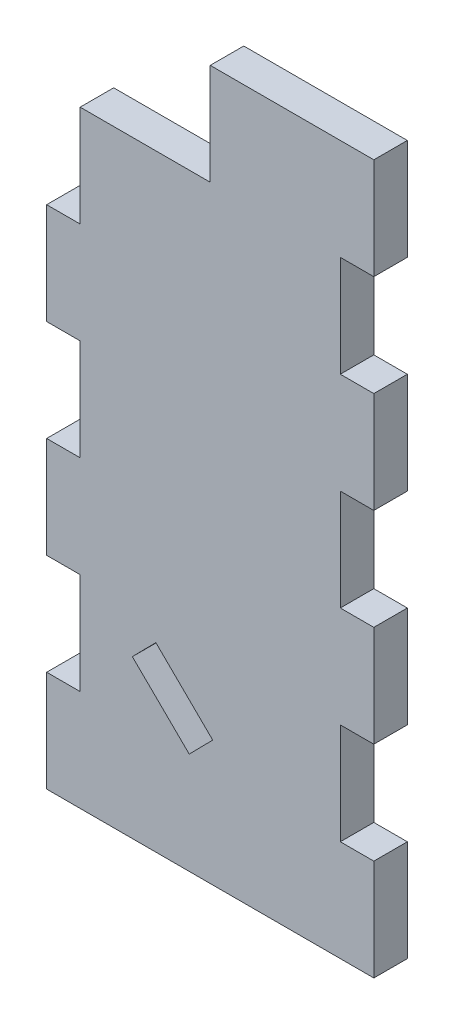
SolidWorks part; units mm, degrees
ref_plane "Front Plane" through (0, 0, 0) normal (0, 0, 1) x (1, 0, 0)
ref_plane "Top Plane" through (0, 0, 0) normal (0, 1, 0) x (1, 0, 0)
ref_plane "Right Plane" through (0, 0, 0) normal (1, 0, 0) x (0, 0, -1)
sketch "Sketch1" plane through (0, 0, 0) normal (0, 0, 1) x (1, 0, 0)
  line L1 (-39.922, 42.4532) -> (12.148, 42.4532)
  line L2 (-39.922, 42.4532) -> (-39.922, -70.3228)
  line L3 (-39.922, -70.3228) -> (12.148, -70.3228)
  line L4 (12.148, 42.4532) -> (12.148, -70.3228)
  dimension "D1" = 112.776
  dimension "D2" = 52.07
extrude "Boss-Extrude1" add sketch "Sketch1" along normal blind 5.334
sketch "Sketch2" plane through (0, 0, 5.334) normal (0, 0, 1) x (1, 0, 0)
  line L0 (-39.922, 42.4532) -> (-39.922, -70.3228) construction
  line L1 (-39.922, 26.3424) -> (-34.588, 26.3424)
  line L2 (-39.922, 26.3424) -> (-39.922, 10.2315)
  line L3 (-39.922, 10.2315) -> (-34.588, 10.2315)
  line L4 (-34.588, 26.3424) -> (-34.588, 10.2315)
  line L5 (-34.588, 26.3424) -> (-34.588, 42.4532) construction
  line L6 (-39.922, -5.8794) -> (-34.588, -5.8794)
  line L7 (-39.922, -5.8794) -> (-39.922, -21.9902)
  line L8 (-39.922, -21.9902) -> (-34.588, -21.9902)
  line L9 (-34.588, -5.8794) -> (-34.588, -21.9902)
  line L10 (-39.922, -38.1011) -> (-34.588, -38.1011)
  line L11 (-39.922, -38.1011) -> (-39.922, -54.2119)
  line L12 (-39.922, -54.2119) -> (-34.588, -54.2119)
  line L13 (-34.588, -38.1011) -> (-34.588, -54.2119)
  line L14 (12.148, 42.4532) -> (-39.922, 42.4532) construction
  line L15 (-34.588, 10.2315) -> (-34.588, -5.8794) construction
  line L16 (-34.588, -21.9902) -> (-34.588, -38.1011) construction
  line L17 (-34.588, -54.2119) -> (-34.588, -70.3228) construction
  line L18 (-39.922, -70.3228) -> (12.148, -70.3228) construction
  line L19 (-13.887, 42.4532) -> (-13.887, -70.3228) construction
  line L20 (6.814, -54.2119) -> (6.814, -70.3228) construction
  line L21 (6.814, -21.9902) -> (6.814, -38.1011) construction
  line L22 (6.814, 10.2315) -> (6.814, -5.8794) construction
  line L23 (6.814, 26.3424) -> (6.814, 42.4532) construction
  line L24 (6.814, -38.1011) -> (6.814, -54.2119)
  line L25 (12.148, -54.2119) -> (6.814, -54.2119)
  line L26 (12.148, -38.1011) -> (12.148, -54.2119)
  line L27 (12.148, -38.1011) -> (6.814, -38.1011)
  line L28 (6.814, -5.8794) -> (6.814, -21.9902)
  line L29 (12.148, -21.9902) -> (6.814, -21.9902)
  line L30 (12.148, -5.8794) -> (12.148, -21.9902)
  line L31 (12.148, -5.8794) -> (6.814, -5.8794)
  line L32 (6.814, 26.3424) -> (6.814, 10.2315)
  line L33 (12.148, 10.2315) -> (6.814, 10.2315)
  line L34 (12.148, 26.3424) -> (12.148, 10.2315)
  line L35 (12.148, 26.3424) -> (6.814, 26.3424)
  line L36 (-34.588, -54.2119) -> (-34.588, -70.3228) construction
  dimension "D1" = 5.334
extrude "Cut-Extrude1" cut sketch "Sketch2" against normal through all
sketch "Sketch3" plane through (0, 0, 5.334) normal (0, 0, 1) x (1, 0, 0)
  line L0 (6.814, -54.2119) -> (6.814, -70.3228) construction
  line L1 (-39.922, -70.3228) -> (12.148, -70.3228) construction
  line L2 (6.814, -70.3228) -> (-39.922, -24.3488) construction
  line L3 (-39.922, -21.9902) -> (-39.922, -38.1011) construction
  line L4 (-22.5448, -41.4427) -> (-13.491, -50.3488)
  line L5 (-22.5448, -41.4427) -> (-26.2854, -45.2453)
  line L6 (-13.491, -50.3488) -> (-17.2316, -54.1514)
  line L7 (-26.2854, -45.2453) -> (-17.2316, -54.1514)
  dimension "D1" = 5.334
  dimension "D2" = 12.7
extrude "Cut-Extrude2" cut sketch "Sketch3" against normal through all
sketch "Sketch4" plane through (0, 0, 5.334) normal (0, 0, 1) x (1, 0, 0)
  line L0 (-39.922, 26.3424) -> (12.148, 26.3424) construction
  line L1 (12.148, 26.3424) -> (6.814, 26.3424) construction
  line L2 (-13.887, 42.4532) -> (-13.887, 26.3424) construction
  line L3 (12.148, 42.4532) -> (-39.922, 42.4532) construction
  line L5 (-39.922, 42.4532) -> (-13.887, 42.4532)
  line L6 (-39.922, 42.4532) -> (-39.922, 26.3424)
  line L7 (-39.922, 26.3424) -> (-13.887, 26.3424)
  line L8 (-13.887, 42.4532) -> (-13.887, 26.3424)
extrude "Cut-Extrude3" cut sketch "Sketch4" against normal through all
equation "\"MDF\"= .21in"
equation "\"Foamcore\"= .13in"
equation "\"Gmaterial\"= \"MDF\""
equation "\"D2@Sketch1\"=\"MDF\"+1.63+\"MDF\""
equation "\"D1@Boss-Extrude1\"=\"MDF\""
equation "\"D1@Sketch2\"=\"MDF\""
equation "\"D1@Sketch3\"=\"MDF\""
equation "\"D2@Sketch3\"=.5"
